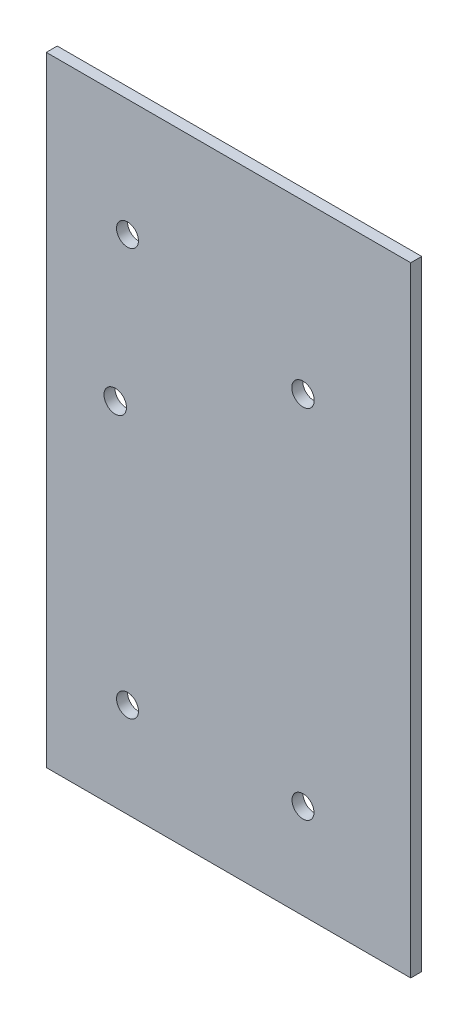
SolidWorks part; units mm, degrees
ref_plane "Front Plane" through (0, 0, 0) normal (0, 0, 1) x (1, 0, 0)
ref_plane "Top Plane" through (0, 0, 0) normal (0, 1, 0) x (1, 0, 0)
ref_plane "Right Plane" through (0, 0, 0) normal (1, 0, 0) x (0, 0, -1)
sketch "Sketch1" plane through (0, 0, 0) normal (0, 0, 1) x (1, 0, 0)
  line L0 (38.1, 146.05) -> (38.1, 95.25) construction
  line L1 (1.8891, 210.8161) -> (107.3869, 210.8161)
  line L2 (1.8891, 210.8161) -> (1.8891, 31.5173)
  line L3 (1.8891, 31.5173) -> (107.3869, 31.5173)
  line L4 (107.3869, 210.8161) -> (107.3869, 31.5173)
  line L6 (38.1, 146.05) -> (88.9, 146.05) construction
  line L7 (88.9, 95.25) -> (88.9, 146.05) construction
  circle A0 centre (25.4, 58.9643) radius 3.175
  circle A1 centre (76.2, 58.9643) radius 3.175
  circle A2 centre (25.4, 176.8929) radius 3.175
  circle A3 centre (21.844, 133.35) radius 3.2512
  circle A4 centre (76.2, 162.306) radius 3.2512
  dimension "D1" = 6.35
  dimension "D6" = 6.5024
  dimension "D2" = 16.256
  dimension "D3" = 12.7
  dimension "D4" = 16.256
  dimension "D5" = 12.7
  dimension "D7" = 33.9233
  dimension "D8" = 23.5109
  dimension "D9" = 27.447
  dimension "D10" = 31.1869
extrude "Boss-Extrude1" add sketch "Sketch1" along normal blind 3.175
equation "\"80/20 to Center Hole\"= .64in"
equation "\"80/20 from Edge\"= 0.5in"
equation "\"D2@Sketch1\"=\"80/20 to Center Hole\""
equation "\"D3@Sketch1\"=\"80/20 from Edge\""
equation "\"D4@Sketch1\"=\"80/20 to Center Hole\""
equation "\"D5@Sketch1\"=\"80/20 from Edge\""
